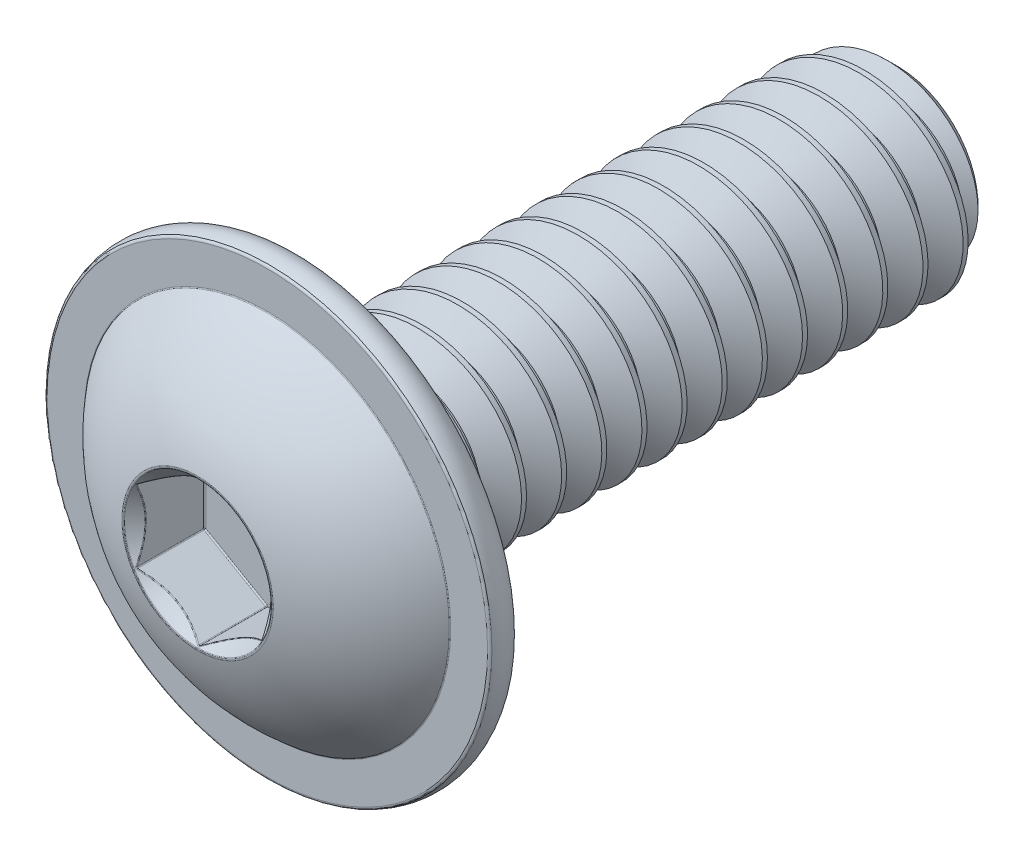
SolidWorks part; units mm, degrees
ref_plane "Front Plane" through (0, 0, 0) normal (0, 0, 1) x (1, 0, 0)
ref_plane "Top Plane" through (0, 0, 0) normal (0, 1, 0) x (1, 0, 0)
ref_plane "Right Plane" through (0, 0, 0) normal (1, 0, 0) x (0, 0, -1)
sketch "Sketch1" plane through (0, 0, 0) normal (1, 0, 0) x (0, 0, -1)
  line L0 (-11.0744, 0) -> (11.0744, 0) construction
  line L1 (11.0744, 0) -> (11.0744, 3.175)
  line L2 (11.0744, 3.175) -> (-7.9756, 3.175)
  line L3 (-7.9756, 3.175) -> (-7.9756, 0)
  line L4 (11.0744, 0) -> (12.3444, 0) construction
  line L5 (11.0744, 2.54) -> (10.4394, 3.175)
  line L6 (-7.9756, 3.175) -> (-7.9756, 7.112)
  line L7 (-7.9756, 7.112) -> (-8.8646, 7.112)
  line L8 (-8.8646, 7.112) -> (-8.8646, 6.223)
  line L9 (-11.0744, 0) -> (-11.0744, 2.2914)
  line L10 (-8.8646, 6.223) -> (-8.8646, 5.334) construction
  line L11 (-11.0744, 2.2914) -> (-13.0588, 1.1457)
  line L12 (-13.0588, 1.1457) -> (-13.0588, -1.1457)
  line L13 (-13.0588, -1.1457) -> (-11.0744, -2.2914)
  line L14 (-11.0744, -2.2914) -> (-9.09, -1.1457)
  line L15 (-9.09, -1.1457) -> (-9.09, 1.1457)
  line L16 (-9.09, 1.1457) -> (-11.0744, 2.2914)
  line L17 (-7.9756, 3.683) -> (-7.9756, -3.683) construction
  circle A1 centre (-11.0744, 0) radius 1.9844 construction
  arc A3 (-8.8646, 5.7785) -> (-11.0744, 2.3906) centre (-4.9503, 0.8107) ccw
  point P2 (0, 0)
  point P10 (9.1694, -3.175)
  point P16 (11.0744, -3.175)
  point P17 (-7.9756, 7.112)
  point P18 (11.0744, 3.175)
  point P20 (9.1694, 3.175)
  dimension "Head Radii" = 6.3246
  dimension "D1" = 45
  dimension "D3" = 0.635
  dimension "D4" = 1.905
  dimension "D2" = 0.0992
sketch "Sketch3" plane through (0, 0, 0) normal (1, 0, 0) x (0, 0, -1)
  line L0 (-7.9756, 3.175) -> (-7.9756, 7.112) construction
  line L1 (-7.9756, 7.112) -> (-8.8646, 7.112) construction
  line L2 (-7.9756, 7.112) -> (-7.9756, 3.683) construction
  line L3 (-11.0744, 0) -> (-11.0744, 2.2914) construction
  line L4 (-7.9756, 3.175) -> (-7.9756, 7.112) construction
  line L5 (-7.9756, 7.112) -> (-8.8646, 7.112) construction
  line L7 (-11.0744, 0) -> (-11.0744, 2.3906)
  line L8 (-7.9756, 3.175) -> (10.4394, 3.175) construction
  line L9 (10.4394, 3.175) -> (11.0744, 2.54)
  line L10 (11.0744, 2.54) -> (11.0744, 0)
  line L11 (11.0744, 0) -> (-11.0744, 0)
  line L12 (-8.8646, 5.7785) -> (-8.8646, 7.112) construction
  line L13 (-7.4676, 3.175) -> (10.4394, 3.175)
  line L14 (-8.8646, 5.7785) -> (-8.8646, 7.0231)
  line L15 (-7.9756, 3.683) -> (-7.9756, 6.9342)
  line L16 (-8.8646, 7.112) -> (-8.8646, 6.9342) construction
  arc A0 (-8.8646, 5.7785) -> (-11.0744, 2.3906) centre (-4.9503, 0.8107) ccw construction
  arc A2 (-8.8646, 7.0231) -> (-7.9756, 6.9342) centre (-8.4901, 6.2787) cw
  arc A4 (-8.8646, 5.7785) -> (-11.0744, 2.3906) centre (-4.9503, 0.8107) ccw
  arc A5 (-7.9756, 3.683) -> (-7.4676, 3.175) centre (-7.4676, 3.683) ccw
  dimension "D1" = 0.1778
revolve "Revolve1" add sketch "Sketch3" angle 360 about L11
sketch "Sketch4" plane through (0, 0, 11.0744) normal (0, 0, 1) x (1, 0, 0)
  line L13 (0, 2.2914) -> (-1.9844, 1.1457)
  line L14 (-1.9844, 1.1457) -> (-1.9844, -1.1457)
  line L15 (-1.9844, -1.1457) -> (0, -2.2914)
  line L16 (0, -2.2914) -> (1.9844, -1.1457)
  line L17 (1.9844, -1.1457) -> (1.9844, 1.1457)
  line L18 (1.9844, 1.1457) -> (0, 2.2914)
  circle A0 centre (0, 0) radius 1.9844 construction
  dimension "D1" = 3.9688
extrude "Cut-Extrude1" cut sketch "Sketch4" against normal up to surface (2.2098 mm away) up to face at (-5.7785, 0, 8.8646)
sketch "Sketch5" plane through (0, 0, 11.0744) normal (0, 0, 1) x (1, 0, 0)
  line L0 (0, 2.2914) -> (0, 2.331) construction
  circle A1 centre (0, 0) radius 2.331
  dimension "D1" = 0.0397
extrude "Cut-Extrude2" cut sketch "Sketch5" against normal up to surface (2.2098 mm away) draft 45 up to face at (0, 0, 8.8646)
fillet "Fillet3" radius 0.0397 21 edges at (-1.1168, -1.6466, 10.7329) (0.8676, -1.7905, 10.7329) (0, -2.2914, 9.9497) (1.9844, -0.0244, 10.7279) (1.9844, -1.1457, 9.9497) (1.1168, 1.6466, 10.7329) (1.9844, 1.1457, 9.9497) (1.9844, 0, 8.8646) (0.9922, -1.7185, 8.8646) (-0.9922, -1.7185, 8.8646) (0.9922, 1.7185, 8.8646) (-1.9844, 0, 8.8646) (-1.9844, -1.1457, 9.9497) (-1.9844, -0.0244, 10.7279) (-0.9922, 1.7185, 8.8646) (-1.9844, 1.1457, 9.9497) (-0.8676, 1.7905, 10.7329) (0, 2.2914, 9.9497) (-2.3906, 0, 11.0744) (2.331, 0, 11.0744) (-5.7785, 0, 8.8646)
fillet "Fillet4" radius 0.0889 2 edges at (-6.9342, 0, 7.9756) (-7.0231, 0, 8.8646)
sketch "Reference Sketch1" plane through (0, 0, 0) normal (0, 0, 1) x (1, 0, 0)
  circle A0 centre (0, 0) radius 7.112 construction
ref_plane "Plane1" through (0, 0, 7.4676) normal (0, 0, 1) x (1, 0, 0)
split "Split1" trim tools "Plane1" bodies to split 106 resulting bodies 108 111
sketch "Sketch6" plane through (0, 0, -11.0744) normal (0, 0, -1) x (-1, 0, 0)
  circle A1 centre (0, 0) radius 3.175
curve "Helix/Spiral1" pitch 1.27 height 20.955 turns 16.5
sketch "Sketch7" plane through (0, 0, 0) normal (1, 0, 0) x (0, 0, -1)
  line L0 (10.995, 3.3125) -> (11.63, 2.2126) construction
  line L1 (11.63, 2.2126) -> (12.265, 3.3125) construction
  line L2 (12.265, 3.3125) -> (10.995, 3.3125) construction
  line L3 (11.0347, 3.2437) -> (12.2253, 3.2437)
  line L4 (12.2253, 3.2437) -> (11.7094, 2.3501)
  line L5 (11.7094, 2.3501) -> (11.5507, 2.3501)
  line L6 (11.5507, 2.3501) -> (11.0347, 3.2437)
  line L7 (11.63, 2.3501) -> (11.63, 2.2126) construction
  line L8 (11.0744, 3.175) -> (12.1857, 3.175) construction
  line L9 (11.63, 3.3125) -> (11.63, 3.175) construction
  point P12 (11.63, 3.2437)
  dimension "D1" = 1.27
  dimension "D2" = 0.1588
sweep "Cut-Sweep1" cut profiles "Sketch7" path "Helix/Spiral1" align with end faces yes
sketch "Sketch8" plane through (0, 0, 7.4676) normal (0, 0, 1) x (1, 0, 0)
  circle A2 centre (0, 0) radius 3.175
  circle A3 centre (0, 0) radius 3.175
  dimension "D1" = 0
extrude "Boss-Extrude1" add sketch "Sketch8" against normal through all draft 45
equation "\"D3@Sketch1\"=0.5*\"Pitch@Sketch1\""
equation "\"D4@Helix/Spiral1\"=\"Pitch@Sketch1\""
equation "\"D3@Helix/Spiral1\"=\"Pitch@Sketch1\"*1.5+\"Length@Sketch1\""
equation "\"D1@Sketch7\"=\"Pitch@Sketch1\""
equation "\"D2@Sketch7\"=\"D1@Sketch7\"/8"
equation "\"D4@Sketch1\"=\"Pitch@Sketch1\"*1.5"
equation "\"D1@Sketch4\"=\"Drive Size@Sketch1\""
equation "\"D1@Sketch5\"=\"Drive Size@Sketch1\"*0.01"
equation "\"D2@Sketch1\"=\"Drive Size@Sketch1\"*0.025"
equation "\"D1@Fillet3\"=\"Drive Size@Sketch1\"*0.01"
equation "\"D1@Fillet4\"=(\"Head Height@Sketch1\"-\"Hex Key Engagement@Sketch1\")*0.1"
equation "\"D1@Sketch3\"=(\"Head Height@Sketch1\"-\"Hex Key Engagement@Sketch1\")*0.2"
